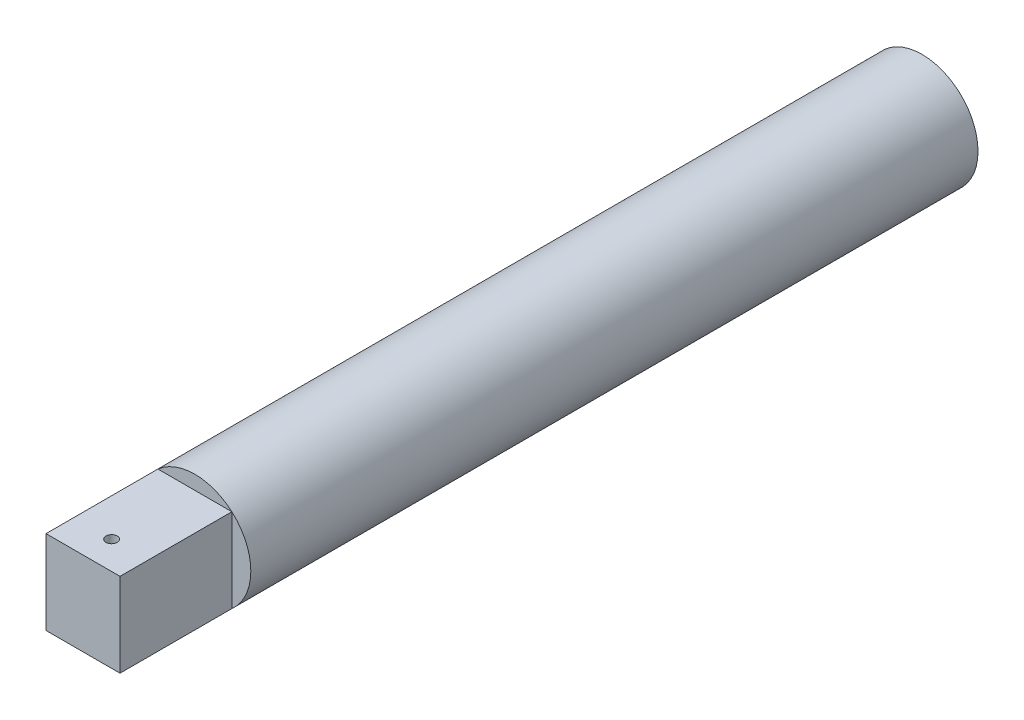
SolidWorks part; units mm, degrees
ref_plane "Front Plane" through (0, 0, 0) normal (0, 0, 1) x (1, 0, 0)
ref_plane "Top Plane" through (0, 0, 0) normal (0, 1, 0) x (1, 0, 0)
ref_plane "Right Plane" through (0, 0, 0) normal (1, 0, 0) x (0, 0, -1)
sketch "Sketch1" plane through (0, 0, 0) normal (0, 0, 1) x (1, 0, 0)
  circle A0 centre (0, 0) radius 10
  dimension "D1" = 20
extrude "Boss-Extrude1" add sketch "Sketch1" along normal blind 150
sketch "Sketch2" plane through (0, 0, 150) normal (0, 0, 1) x (1, 0, 0)
  line L1 (-6.6144, 7.5) -> (6.6144, 7.5)
  line L2 (-6.6144, 7.5) -> (-6.6144, -7.5)
  line L3 (-6.6144, -7.5) -> (6.6144, -7.5)
  line L4 (6.6144, 7.5) -> (6.6144, -7.5)
  circle A0 centre (0, 0) radius 10 construction
  circle A1 centre (0, 0) radius 10
  point P0 (0, 0)
  circle M3 centre (0, 0) radius 10
  dimension "D1" = 15
extrude "Cut-Extrude1" cut sketch "Sketch2" against normal blind 20 contours L1 M3 | L4 M3 | L3 M3 | L2 M3 region at (0, 8.5116, 150) region at (-7.9904, 0, 150) region at (7.9904, 0, 150) region at (0, -8.5116, 150)
sketch "Sketch3" plane through (0, 7.5, 0) normal (0, 1, 0) x (1, 0, 0)
  line L0 (6.6144, -130) -> (6.6144, -150) construction
  line L1 (-6.6144, -150) -> (6.6144, -150) construction
  circle A0 centre (0.1144, -145) radius 2
  circle A1 centre (0.1144, -145) radius 1
  dimension "D3" = 4
  dimension "D4" = 2
  dimension "D1" = 6.5
  dimension "D2" = 5
extrude "Cut-Extrude2" [suppressed] cut sketch "Sketch3" against normal blind 2.5
extrude "Cut-Extrude4" cut sketch "Sketch3<3>" along direction (0, -1, 0) on the side against the normal through all contours A1 region at (0.1144, 7.5, 145)
sketch "Sketch3<3>" plane through (0, 7.5, 0) normal (0, 1, 0) x (1, 0, 0) same geometry as "Sketch3"
sketch "Sketch7" plane through (0, 0, 0) normal (0, 0, -1) x (-1, 0, 0)
  circle A0 centre (5, 0) radius 1
  circle A1 centre (-5, 0) radius 1
  dimension "D1" = 2
  dimension "D2" = 2
  dimension "D3" = 10
  dimension "D4" = 5
extrude "Cut-Extrude5" cut sketch "Sketch7" against normal blind 10
